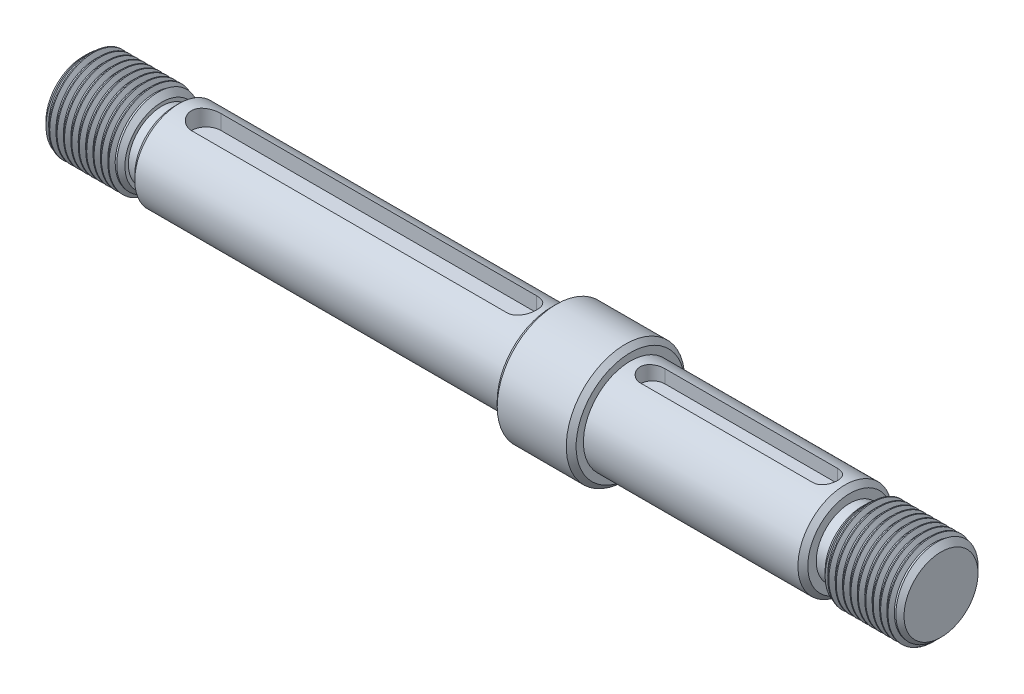
SolidWorks part; units mm, degrees
material "1.0503 (C45)"
ref_plane "前视基准面" through (0, 0, 0) normal (0, 0, 1) x (1, 0, 0)
ref_plane "上视基准面" through (0, 0, 0) normal (0, 1, 0) x (1, 0, 0)
ref_plane "右视基准面" through (0, 0, 0) normal (1, 0, 0) x (0, 0, -1)
sketch "轴轴向刨面" plane through (0, 0, 0) normal (0, 0, 1) x (1, 0, 0)
  line L0 (0, 0) -> (0, 9)
  line L3 (18.5, 9) -> (95, 9)
  line L4 (95, 9) -> (95, 12)
  line L5 (95, 12) -> (111, 12)
  line L6 (111, 12) -> (111, 9.52)
  line L7 (111, 9.52) -> (155.5, 9.52)
  line L8 (174, 9) -> (174, 0)
  line L9 (174, 0) -> (0, 0)
  line L10 (158, 9) -> (174, 9)
  line L12 (18.5, 6.8) -> (16, 6.8)
  line L13 (16, 6.8) -> (16, 9)
  line L14 (0, 9) -> (16, 9)
  line L16 (155.5, 9.52) -> (155.5, 6.8)
  line L17 (155.5, 6.8) -> (158, 6.8)
  line L18 (158, 6.8) -> (158, 9)
  line L19 (18.5, 9) -> (18.5, 6.8)
  dimension "D1" = 44.5
  dimension "D2" = 9
  dimension "D3" = 76.5
  dimension "D4" = 16
  dimension "D5" = 2.5
  dimension "D7" = 2.2
  dimension "D8" = 9.52
  dimension "轴肩半径" = 24
  dimension "大端螺纹长度" = 16
revolve "旋转轴" add sketch "轴轴向刨面" angle 360 about L9
ref_plane "9mm键槽面" through (0, 9, 0) normal (0, 1, 0) x (1, 0, 0)
sketch "草图24" plane through (0, 9, 0) normal (0, 1, 0) x (1, 0, 0)
  line L0 (25, 0) -> (89, 0) construction
  line L3 (25, 3) -> (89, 3)
  line L4 (25, -3) -> (89, -3)
  line L5 (18.5, 6.8) -> (18.5, -6.8) construction
  line L6 (95, 12) -> (95, -12) construction
  arc A2 (25, 3) -> (25, -3) centre (25, 0) ccw
  arc A3 (89, -3) -> (89, 3) centre (89, 0) ccw
  point P2 (57, 0)
  point P11 (22, 0)
  point P12 (92, 0)
  dimension "D2" = 6
  dimension "D1" = 3.5
  dimension "D3" = 3
  dimension "D4" = 70
extrude "切除-拉伸11" cut sketch "草图24" against normal blind 3.5
ref_plane "9.52mm键槽面" through (0, 9.52, 0) normal (0, 1, 0) x (1, 0, 0)
sketch "草图25" plane through (0, 9.52, 0) normal (0, 1, 0) x (1, 0, 0)
  line L0 (115.5, 0) -> (150.5, 0) construction
  line L1 (111, 0) -> (155.5, 0) construction
  line L2 (115.5, 2.5) -> (150.5, 2.5)
  line L3 (115.5, -2.5) -> (150.5, -2.5)
  line L5 (155.5, -9.52) -> (155.5, 9.52) construction
  line L6 (111, -9.52) -> (111, 9.52) construction
  arc A0 (115.5, 2.5) -> (115.5, -2.5) centre (115.5, 0) ccw
  arc A1 (150.5, -2.5) -> (150.5, 2.5) centre (150.5, 0) ccw
  point P5 (133, 0)
  point P14 (153, 0)
  point P15 (113, 0)
  dimension "D2" = 2
  dimension "D1" = 5
  dimension "D3" = 2.5
  dimension "D4" = 40
extrude "切除-拉伸12" cut sketch "草图25" against normal blind 3
sketch "草图30" plane through (0, 0, 0) normal (-1, 0, 0) x (0, 0, 1)
  circle A0 centre (0, 0) radius 9 construction
  circle A1 centre (0, 0) radius 9
chamfer "倒角1" distance 1.5 angle 45 4 edges at (174, 0, -9) (158, 0, -9) (16, 0, -9) (0, 0, -9)
chamfer "倒角2" distance 1 angle 45 4 edges at (18.5, 0, -9) (95, 0, -12) (111, 0, -12) (155.5, 0, -9.52)
thread "螺纹线1" pitch 1.5 method cut profile "螺纹线轮廓1" start angle 0, offset 1.5, length 16, pitch 1.5, diameter 18
ref_plane "基准面1" through (0, 0, -9) normal (0, -1, 0) x (0, 0, -1)
sketch "螺纹线轮廓1" plane through (0, 0, -9) normal (0, -1, 0) x (0, 0, -1)
  line L0 (0, 0) -> (0, 1.5) construction
  line L11 (0, 0) -> (0, 1.3125)
  line L12 (0, 1.3125) -> (-0.8119, 0.8437)
  line L13 (-0.8119, 0.8437) -> (-0.8119, 0.4687)
  line L15 (-0.8119, 0.4687) -> (0, 0)
  line L17 (-0.8119, 0.6562) -> (0, 0.6562) construction
  point P2 (0, 0)
  dimension "Pitch" = 1.5
  dimension "Profile_Angle" = 60
  dimension "Profile_Land" = 0.375
  dimension "Profile_Height" = 0.8119
thread "螺纹线2" pitch 1.5 method cut profile "螺纹线轮廓2" start angle 0, offset 1.5, length 16, pitch 1.5, diameter 18
ref_plane "基准面2" through (158, 0, -9) normal (0, -1, 0) x (0, 0, -1)
sketch "螺纹线轮廓2" plane through (158, 0, -9) normal (0, -1, 0) x (0, 0, -1)
  line L0 (0, 0) -> (0, 1.5) construction
  line L11 (0, 0) -> (0, 1.3125)
  line L12 (0, 1.3125) -> (-0.8119, 0.8437)
  line L13 (-0.8119, 0.8437) -> (-0.8119, 0.4687)
  line L15 (-0.8119, 0.4687) -> (0, 0)
  line L17 (-0.8119, 0.6562) -> (0, 0.6562) construction
  point P2 (0, 0)
  dimension "Pitch" = 1.5
  dimension "Profile_Angle" = 60
  dimension "Profile_Land" = 0.375
  dimension "Profile_Height" = 0.8119
